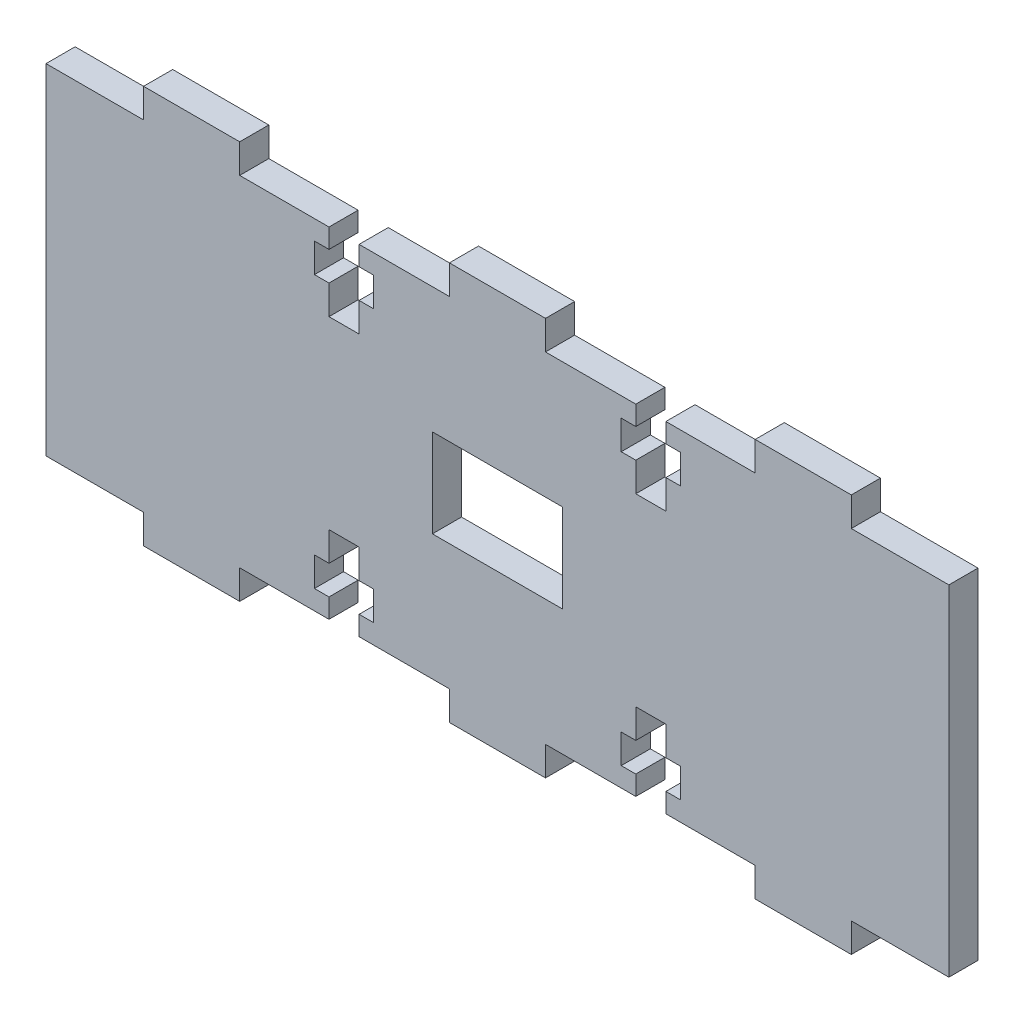
SolidWorks part; units mm, degrees
ref_plane "Plano frontal" through (0, 0, 0) normal (0, 0, 1) x (1, 0, 0)
ref_plane "Plano superior" through (0, 0, 0) normal (0, 1, 0) x (1, 0, 0)
ref_plane "Plano direito" through (0, 0, 0) normal (1, 0, 0) x (0, 0, -1)
sketch "Esboço1" plane through (0, 0, 0) normal (0, 0, 1) x (1, 0, 0)
  line L0 (19.95, 35) -> (41.55, 35)
  line L1 (0, 0) -> (10.05, 0)
  line L2 (0, 0) -> (0, 35)
  line L3 (0, 35) -> (10.05, 35)
  line L4 (93, 0) -> (93, 35)
  line L6 (10.05, 0) -> (10.05, -3)
  line L7 (10.05, -3) -> (19.95, -3)
  line L8 (19.95, 0) -> (19.95, -3)
  line L9 (19.95, 0) -> (41.55, 0)
  line L10 (41.55, 0) -> (41.55, -3)
  line L11 (41.55, -3) -> (51.45, -3)
  line L12 (51.45, 0) -> (51.45, -3)
  line L13 (51.45, 0) -> (73.05, 0)
  line L14 (73.05, 0) -> (73.05, -3)
  line L15 (73.05, -3) -> (82.95, -3)
  line L16 (82.95, 0) -> (82.95, -3)
  line L17 (82.95, 35) -> (93, 35)
  line L18 (10.05, 35) -> (10.05, 38)
  line L19 (10.05, 38) -> (19.95, 38)
  line L20 (19.95, 35) -> (19.95, 38)
  line L21 (82.95, 0) -> (93, 0)
  line L22 (41.55, 35) -> (41.55, 38)
  line L23 (41.55, 38) -> (51.45, 38)
  line L24 (51.45, 35) -> (51.45, 38)
  line L26 (73.05, 35) -> (73.05, 38)
  line L27 (73.05, 38) -> (82.95, 38)
  line L28 (82.95, 35) -> (82.95, 38)
  line L29 (51.45, 35) -> (73.05, 35)
  dimension "D1" = 9.9
  dimension "D2" = 3
  dimension "D3" = 3
  dimension "D4" = 35
  dimension "D5" = 93
  dimension "D6" = 10.05
  dimension "D7" = 10.05
  dimension "D8" = 21.6
extrude "Ressalto-extrusão1" add sketch "Esboço1" along normal blind 3
sketch "Esboço3" plane through (0, 0, 0) normal (0, 0, -1) x (-1, 0, 0)
  text T0 "Garagem 55" font "Freehand521 BT" height 3.5
extrude "Corte-extrusão1" cut sketch "Esboço3" against normal blind 1.5
sketch "Esboço4" plane through (0, 0, 0) normal (0, 0, -1) x (-1, 0, 0)
  text T0 "Apoio:" font "Arial Black" height in points 8
extrude "Corte-extrusão2" cut sketch "Esboço4" against normal blind 1.5
sketch "Esboço5" plane through (0, 0, 0) normal (0, 0, -1) x (-1, 0, 0)
  line L0 (-73.05, 35) -> (-51.45, 35) construction
  line L1 (-63.85, 35) -> (-60.75, 35)
  line L2 (-63.85, 35) -> (-63.85, 33)
  line L3 (-60.75, 33) -> (-59.25, 33)
  line L4 (-60.75, 35) -> (-60.75, 33)
  line L5 (-41.55, 35) -> (-19.95, 35) construction
  line L6 (-65.35, 33) -> (-63.85, 33)
  line L7 (-65.35, 33) -> (-65.35, 30)
  line L8 (-65.35, 30) -> (-63.85, 30)
  line L9 (-59.25, 33) -> (-59.25, 30)
  line L10 (-32.25, 35) -> (-29.15, 35)
  line L11 (-32.25, 35) -> (-32.25, 33)
  line L12 (-29.15, 33) -> (-27.65, 33)
  line L13 (-29.15, 35) -> (-29.15, 33)
  line L14 (-51.45, 0) -> (-73.05, 0) construction
  line L15 (-33.75, 33) -> (-32.25, 33)
  line L16 (-33.75, 33) -> (-33.75, 30)
  line L17 (-33.75, 30) -> (-32.25, 30)
  line L18 (-27.65, 33) -> (-27.65, 30)
  line L19 (-63.85, 0) -> (-60.75, 0)
  line L20 (-63.85, 0) -> (-63.85, 2)
  line L21 (-63.85, 2) -> (-65.35, 2)
  line L22 (-60.75, 0) -> (-60.75, 2)
  line L23 (-19.95, 0) -> (-41.55, 0) construction
  line L24 (-59.25, 2) -> (-60.75, 2)
  line L25 (-59.25, 2) -> (-59.25, 5)
  line L26 (-59.25, 5) -> (-60.75, 5)
  line L27 (-65.35, 2) -> (-65.35, 5)
  line L28 (-32.25, 0) -> (-29.15, 0)
  line L29 (-32.25, 0) -> (-32.25, 2)
  line L30 (-32.25, 2) -> (-33.75, 2)
  line L31 (-29.15, 0) -> (-29.15, 2)
  line L32 (-73.05, 0) -> (-73.05, -3) construction
  line L33 (-27.65, 2) -> (-29.15, 2)
  line L34 (-27.65, 2) -> (-27.65, 5)
  line L35 (-27.65, 5) -> (-29.15, 5)
  line L36 (-33.75, 2) -> (-33.75, 5)
  line L37 (-19.95, -3) -> (-19.95, 0) construction
  line L38 (-63.85, 5) -> (-65.35, 5)
  line L40 (-73.05, 38) -> (-73.05, 35) construction
  line L41 (-19.95, 35) -> (-19.95, 38) construction
  line L42 (-29.15, 30) -> (-27.65, 30)
  line L43 (-63.85, 30) -> (-63.85, 27)
  line L44 (-63.85, 27) -> (-60.75, 27)
  line L45 (-60.75, 30) -> (-60.75, 27)
  line L46 (-53.2, 22.05) -> (-39.8, 22.05)
  line L47 (-32.25, 30) -> (-32.25, 27)
  line L48 (-32.25, 27) -> (-29.15, 27)
  line L49 (-29.15, 30) -> (-29.15, 27)
  line L50 (-60.75, 30) -> (-59.25, 30)
  line L51 (-32.25, 5) -> (-32.25, 8)
  line L52 (-32.25, 8) -> (-29.15, 8)
  line L53 (-29.15, 5) -> (-29.15, 8)
  line L54 (-32.25, 5) -> (-33.75, 5)
  line L55 (-63.85, 5) -> (-63.85, 8)
  line L56 (-63.85, 8) -> (-60.75, 8)
  line L57 (-60.75, 5) -> (-60.75, 8)
  line L58 (-53.2, 22.05) -> (-53.2, 12.95)
  line L59 (-53.2, 12.95) -> (-39.8, 12.95)
  line L60 (-39.8, 22.05) -> (-39.8, 12.95)
  line L61 (0, 35) -> (0, 0) construction
  dimension "D1" = 3.1
  dimension "D2" = 3.1
  dimension "D3" = 3.1
  dimension "D4" = 3.1
  dimension "D5" = 9.2
  dimension "D6" = 9.2
  dimension "D7" = 9.2
  dimension "D8" = 9.2
  dimension "D9" = 2
  dimension "D10" = 2
  dimension "D11" = 2
  dimension "D12" = 2
  dimension "D13" = 6.1
  dimension "D14" = 1.5
  dimension "D15" = 1.5
  dimension "D16" = 6.1
  dimension "D17" = 1.5
  dimension "D18" = 6.1
  dimension "D19" = 1.5
  dimension "D20" = 6.1
  dimension "D21" = 3
  dimension "D22" = 3
  dimension "D23" = 3
  dimension "D24" = 3
  dimension "D25" = 3
  dimension "D26" = 3
  dimension "D27" = 3
  dimension "D28" = 3
  dimension "D29" = 3.1
  dimension "D30" = 1.5
  dimension "D31" = 3.1
  dimension "D32" = 1.5
  dimension "D33" = 3.1
  dimension "D34" = 1.5
  dimension "D35" = 3.1
  dimension "D36" = 1.5
  dimension "D37" = 13.4
  dimension "D38" = 9.1
  dimension "D39" = 12.95
  dimension "D40" = 39.8
extrude "Corte-extrusão3" cut sketch "Esboço5" against normal through all
sketch "Esboço7" plane through (0, 0, 0) normal (0, 0, -1) x (-1, 0, 0)
  line L0 (-82.95, 0) -> (-93, 0) construction
  line L1 (-93, 0) -> (-93, 35) construction
  text T0 "GERSE" font "Bauhaus 93" height in points 14
  dimension "D1" = 2
  dimension "D2" = 6
extrude "Corte-extrusão4" cut sketch "Esboço7" against normal blind 2.5
sketch "Esboço8" plane through (0, 0, 0) normal (0, 0, -1) x (-1, 0, 0)
  line L0 (-98.05, 0) -> (4.95, 0) construction
  line L1 (-53.2, 22.05) -> (-53.2, 12.95) construction
  text T0 "IFSP\r\nGRU" font "Bauhaus 93" height 3.5
  dimension "D1" = 7.5
  dimension "D2" = 2
extrude "Corte-extrusão5" cut sketch "Esboço8" against normal blind 2
